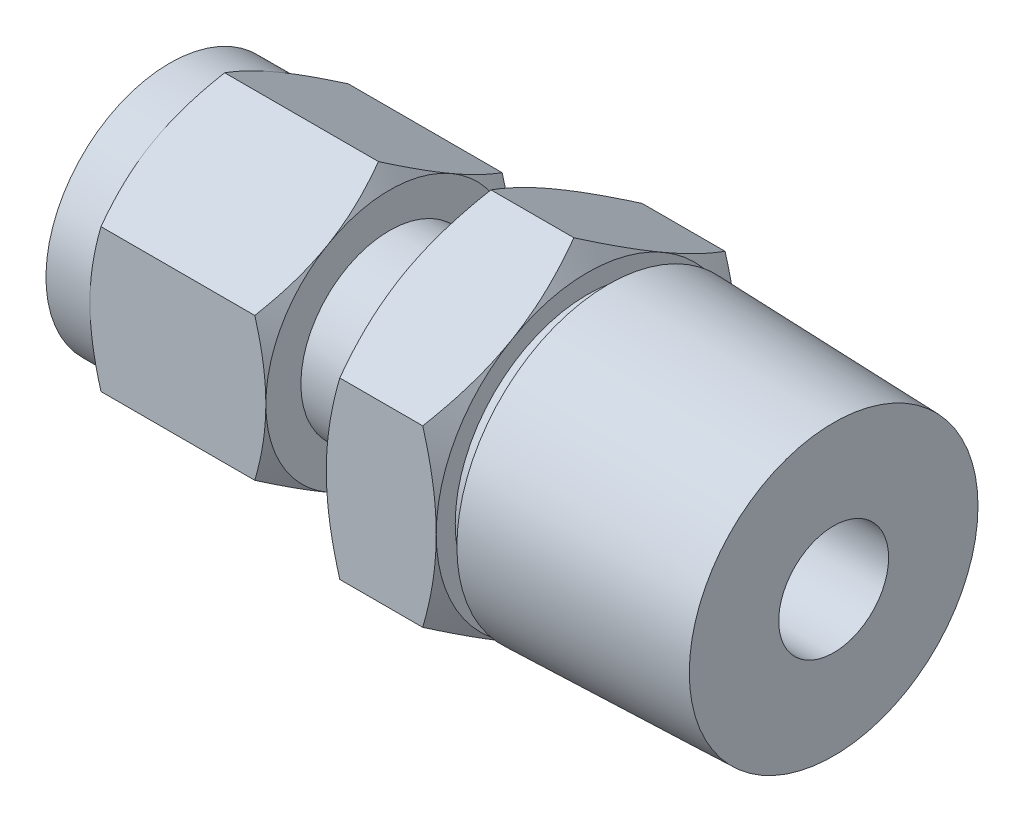
SolidWorks part; units mm, degrees
material "Brass"
ref_plane "Front Plane" through (0, 0, 0) normal (0, 0, 1) x (1, 0, 0)
ref_plane "Top Plane" through (0, 0, 0) normal (0, 1, 0) x (1, 0, 0)
ref_plane "Right Plane" through (0, 0, 0) normal (1, 0, 0) x (0, 0, -1)
sketch "Sketch5" plane through (0, 0, 0) normal (0, 0, 1) x (1, 0, 0)
  line L0 (0, 0) -> (-7.7637, 0) construction
  line L1 (-7.3838, -3.175) -> (-7.3838, -2.921)
  line L2 (-7.3838, -2.921) -> (-14.224, -2.921)
  line L5 (-13.02, -8.7427) -> (0, -8.3381)
  line L6 (0, -8.3381) -> (0, -3.175)
  line L8 (-13.6602, -7.634) -> (-13.02, -8.7427)
  line L10 (-14.224, -7.634) -> (-13.6602, -7.634)
  line L12 (-14.224, -2.921) -> (-14.224, -7.634)
  line L16 (0, -3.175) -> (-7.3838, -3.175)
  dimension "D2" = 0.254
  dimension "pipe-a" = 13.02
  dimension "pipe-b" = 14.224
  dimension "pipe thread dia" = 17.4854
  dimension "D7" = 120
  dimension "pipe-neck down" = 15.2679
  dimension "mate ref dist" = 7.3838
revolve "Revolve1" add sketch "Sketch5" angle 360 about L0
cosmetic thread "Cosmetic Thread1" parameters "D2"=14.6721
sketch "Sketch16" plane through (-14.224, 0, 0) normal (-1, 0, 0) x (0, 0, 1)
  line L1 (0, 10.082) -> (-8.7312, 5.041)
  line L2 (-8.7312, 5.041) -> (-8.7312, -5.041)
  line L3 (-8.7312, -5.041) -> (0, -10.082)
  line L4 (0, -10.082) -> (8.7312, -5.041)
  line L5 (8.7312, -5.041) -> (8.7312, 5.041)
  line L6 (8.7312, 5.041) -> (0, 10.082)
  circle A0 centre (0, 0) radius 8.7312 construction
  circle A1 centre (0, 0) radius 2.921 construction
  circle A2 centre (0, 0) radius 2.921
  dimension "pipe hex" = 17.4625
extrude "Extrude6" add sketch "Sketch16" along normal blind 6.35
sketch "Sketch17" plane through (-20.574, 0, 0) normal (-1, 0, 0) x (0, 0, 1)
  line L0 (8.7312, 5.041) -> (0, 10.082) construction
  circle A0 centre (0, 0) radius 8.7312
extrude "Extrude7" cut sketch "Sketch17" against normal blind 6.35 draft 60 flip side to cut
sketch "Sketch18" plane through (-14.224, 0, 0) normal (1, 0, 0) x (0, 0, -1)
  line L0 (-8.7312, 5.041) -> (0, 10.082) construction
  circle A0 centre (0, 0) radius 8.7312
extrude "Extrude8" cut sketch "Sketch18" against normal blind 6.35 draft 60 flip side to cut
ref_plane "Plane2" through (-25.654, 0, 0) normal (1, 0, 0) x (0, 0, -1)
sketch "Sketch6" plane through (-25.654, 0, 0) normal (1, 0, 0) x (0, 0, -1)
  line L1 (0, -8.2489) -> (7.1437, -4.1244)
  line L2 (7.1437, -4.1244) -> (7.1438, 4.1244)
  line L3 (7.1438, 4.1244) -> (0, 8.2489)
  line L4 (0, 8.2489) -> (-7.1437, 4.1244)
  line L5 (-7.1437, 4.1244) -> (-7.1437, -4.1244)
  line L6 (-7.1437, -4.1244) -> (0, -8.2489)
  circle A0 centre (0, 0) radius 7.1438 construction
  circle A1 centre (0, 0) radius 2.921 construction
  circle A2 centre (0, 0) radius 2.921
  dimension "tube hex" = 14.2875
extrude "Extrude1" add sketch "Sketch6" against normal blind 10.16
sketch "Sketch8" plane through (-35.814, 0, 0) normal (-1, 0, 0) x (0, 0, 1)
  line L0 (0, 8.2489) -> (7.1437, 4.1244) construction
  circle A0 centre (0, 0) radius 7.1437
extrude "Extrude2" cut sketch "Sketch8" against normal blind 1.524 draft 60 flip side to cut
sketch "Sketch9" plane through (-25.654, 0, 0) normal (1, 0, 0) x (0, 0, -1)
  line L0 (0, 8.2489) -> (-7.1437, 4.1244) construction
  circle A0 centre (0, 0) radius 7.1437
extrude "Extrude3" cut sketch "Sketch9" against normal blind 6.35 draft 60 flip side to cut
sketch "Sketch11" plane through (0, 0, 0) normal (0, 0, 1) x (1, 0, 0)
  line L0 (-25.654, 2.921) -> (-35.814, 2.921) construction
  line L2 (-21.463, 4.4983) -> (-21.8897, 5.2375)
  line L3 (-14.224, 4.4983) -> (-21.463, 4.4983)
  line L4 (0, -8.3381) -> (0, 8.3381) construction
  line L5 (-21.8897, 5.2375) -> (-30.734, 4.9626)
  line L6 (-14.224, -7.634) -> (-14.224, 7.634) construction
  line L7 (-30.734, 8.2489) -> (-30.734, 7.2099) construction
  line L8 (-38.354, 2.921) -> (-14.224, 2.921)
  line L9 (-35.1759, 8.2489) -> (-26.2921, 8.2489) construction
  line L11 (-30.734, 7.1437) -> (-38.354, 7.1437)
  line L12 (-30.734, 7.1437) -> (-30.734, 4.9626)
  line L13 (-38.354, 7.1437) -> (-38.354, 2.921)
  line L14 (-14.224, 4.4983) -> (-14.224, 2.921)
  line L17 (0, 0) -> (-14.224, 0) construction
  dimension "tube-dia" = 14.2875
  dimension "OAL" = 38.354
  dimension "D6" = 120
  dimension "tube-neck down" = 8.9967
  dimension "tube-c" = 16.4643
  dimension "tube taper dia" = 10.475
revolve "Revolve2" add sketch "Sketch11" angle 360 about L17
sketch "Sketch15" plane through (-38.354, 0, 0) normal (-1, 0, 0) x (0, 0, 1)
  circle A0 centre (0, 0) radius 3.175
extrude "Extrude5" cut sketch "Sketch15" against normal blind 15.24
sketch "Sketch19" plane through (-14.224, 0, 0) normal (1, 0, 0) x (0, 0, -1)
  point P0 (0, 0)
other "RPoint1"
other "CPoint1" parameters "Diameter"=6.35, "StubLength"=23.8125
ref_axis "Axis1" through (-33.114, 0, 0) along (1, 0, 0)
ref_axis "Axis of Rotation" through (-13.02, 0, 0) along (1, 0, 0)
